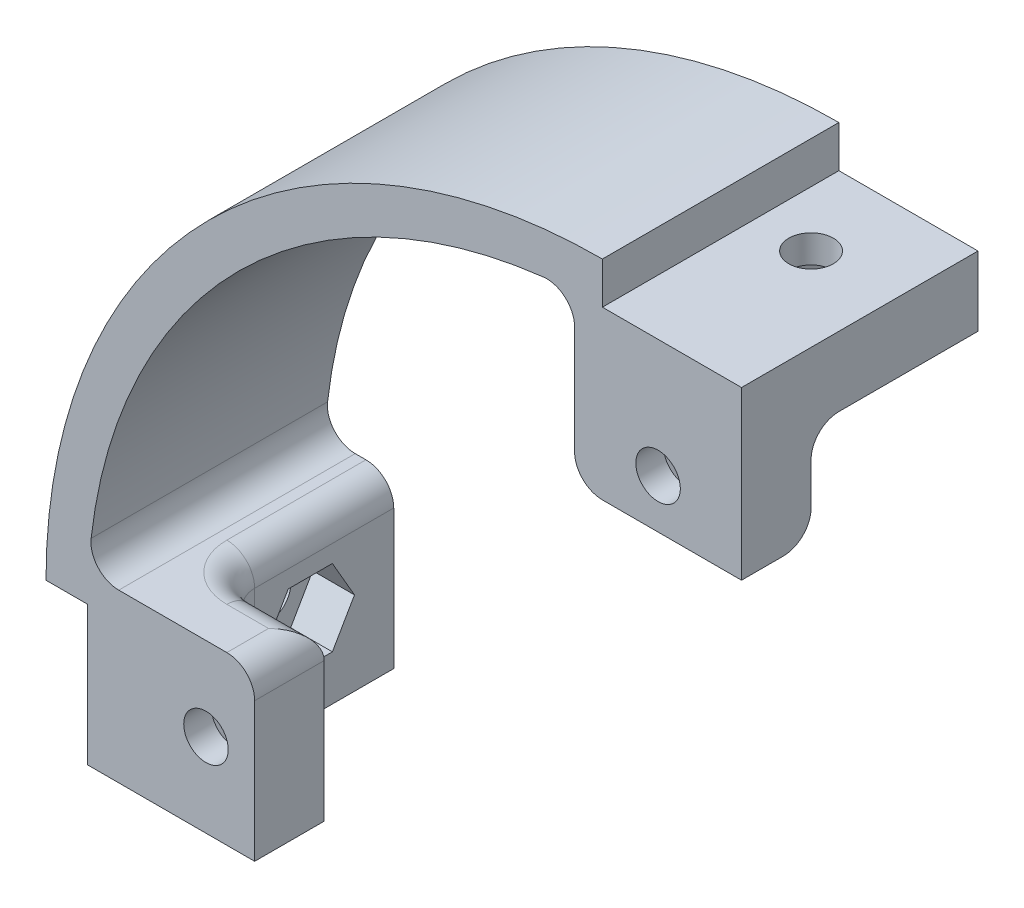
SolidWorks part; units mm, degrees
note: The reader was unsure of these and kept them because the rebuilt part matched: shared geometry of "Sketch4<3>", "Sketch6<3>", "Sketch8<3>", "Sketch9<3>".
ref_plane "Front Plane" through (0, 0, 0) normal (0, 0, 1) x (1, 0, 0)
ref_plane "Top Plane" through (0, 0, 0) normal (0, 1, 0) x (1, 0, 0)
ref_plane "Right Plane" through (0, 0, 0) normal (1, 0, 0) x (0, 0, -1)
sketch "Sketch1" plane through (0, 0, 0) normal (0, 0, 1) x (1, 0, 0)
  line L0 (0, 0) -> (3, 0)
  line L1 (40, 40) -> (40, 37)
  arc A0 (0, 0) -> (40, 40) centre (40, 0) cw
  arc A1 (3, 0) -> (40, 37) centre (40, 0) cw
  point P8 (40, 38.5)
  dimension "D1" = 40
  dimension "D2" = 3
extrude "Boss-Extrude1" add sketch "Sketch1" along normal blind 17
sketch "Sketch2" plane through (0, 0, 0) normal (0, -1, 0) x (1, 0, 0)
  line L0 (0, 0) -> (3, 0) construction
  line L1 (3, 17) -> (8, 17)
  line L2 (3, 17) -> (3, 0)
  line L3 (3, 0) -> (8, 0)
  line L4 (8, 17) -> (8, 0)
  line L5 (3, 17) -> (3, 0) construction
  line L6 (0, 17) -> (3, 17) construction
  dimension "D1" = 5
extrude "Boss-Extrude2" add sketch "Sketch2" along normal blind 10 and the other way blind 2
sketch "Sketch3" plane through (40, 0, 0) normal (1, 0, 0) x (0, 0, -1)
  line L0 (-17, 37) -> (-17, 40) construction
  line L1 (0, 37) -> (-17, 37)
  line L2 (0, 37) -> (0, 32)
  line L3 (0, 32) -> (-17, 32)
  line L4 (-17, 37) -> (-17, 32)
  dimension "D1" = 5
extrude "Boss-Extrude3" add sketch "Sketch3" along normal blind 10 and the other way blind 2
sketch "Sketch4" plane through (8, 0, 0) normal (1, 0, 0) x (0, 0, -1)
  line L1 (-17, 2) -> (-17, -10) construction
  line L2 (0, 2) -> (0, -10) construction
  line L4 (-4.4123, -6.75) -> (-2.8246, -4)
  line L5 (-2.8246, -4) -> (-4.4123, -1.25)
  line L6 (-4.4123, -1.25) -> (-7.5877, -1.25)
  line L7 (-7.5877, -1.25) -> (-9.1754, -4)
  line L8 (-9.1754, -4) -> (-7.5877, -6.75)
  line L9 (-7.5877, -6.75) -> (-4.4123, -6.75)
  circle A1 centre (-6, -4) radius 1.6
  circle A2 centre (-6, -4) radius 2.75 construction
  point P9 (-17, -4)
  dimension "D2" = 3.2
  dimension "D3" = 6
  dimension "D4" = 5.5
extrude "Cut-Extrude1" cut sketch "Sketch4" against normal blind 3
extrude "Cut-Extrude2" cut sketch "Sketch4<3>" against normal through all contours A1
sketch "Sketch4<3>" plane through (8, 0, 0) normal (1, 0, 0) x (0, 0, -1) same geometry as "Sketch4"
sketch "Sketch5" plane through (8, 0, 0) normal (1, 0, 0) x (0, 0, -1)
  line L0 (0, -10) -> (-17, -10) construction
  line L1 (-17, 2) -> (-12, 2)
  line L2 (-17, 2) -> (-17, -10)
  line L3 (-17, -10) -> (-12, -10)
  line L4 (-12, 2) -> (-12, -10)
  dimension "D1" = 5
extrude "Boss-Extrude4" add sketch "Sketch5" along normal blind 7
sketch "Sketch6" plane through (0, 0, 12) normal (0, 0, -1) x (-1, 0, 0)
  line L0 (-15, -10) -> (-8, -10) construction
  line L1 (-15, -10) -> (-15, 2) construction
  line L3 (-9.9123, -6.75) -> (-8.3246, -4)
  line L4 (-8.3246, -4) -> (-9.9123, -1.25)
  line L5 (-9.9123, -1.25) -> (-13.0877, -1.25)
  line L6 (-13.0877, -1.25) -> (-14.6754, -4)
  line L7 (-14.6754, -4) -> (-13.0877, -6.75)
  line L8 (-13.0877, -6.75) -> (-9.9123, -6.75)
  circle A1 centre (-11.5, -4) radius 1.6
  circle A2 centre (-11.5, -4) radius 2.75 construction
  point P5 (-11.5, -10)
  point P8 (-15, -4)
  dimension "D2" = 3.2
  dimension "D3" = 5.5
extrude "Cut-Extrude3" cut sketch "Sketch6" against normal blind 3
extrude "Cut-Extrude4" cut sketch "Sketch6<3>" against normal through all contours A1
sketch "Sketch6<3>" plane through (0, 0, 12) normal (0, 0, -1) x (-1, 0, 0) same geometry as "Sketch6"
sketch "Sketch7" plane through (0, 32, 0) normal (0, -1, 0) x (1, 0, 0)
  line L0 (38, 17) -> (38, 0) construction
  line L1 (50, 17) -> (38, 17)
  line L2 (50, 17) -> (50, 12)
  line L3 (50, 12) -> (38, 12)
  line L4 (38, 17) -> (38, 12)
  dimension "D1" = 5
extrude "Boss-Extrude5" add sketch "Sketch7" along normal blind 7
sketch "Sketch8" plane through (0, 32, 0) normal (0, -1, 0) x (1, 0, 0)
  line L0 (38, 0) -> (50, 0) construction
  line L2 (42.4123, 8.75) -> (40.8246, 6)
  line L3 (40.8246, 6) -> (42.4123, 3.25)
  line L4 (42.4123, 3.25) -> (45.5877, 3.25)
  line L5 (45.5877, 3.25) -> (47.1754, 6)
  line L6 (47.1754, 6) -> (45.5877, 8.75)
  line L7 (45.5877, 8.75) -> (42.4123, 8.75)
  circle A1 centre (44, 6) radius 1.6
  circle A2 centre (44, 6) radius 2.75 construction
  point P5 (44, 0)
  dimension "D2" = 3.2
  dimension "D3" = 6
  dimension "D4" = 5.5
extrude "Cut-Extrude5" cut sketch "Sketch8" against normal blind 3
extrude "Cut-Extrude6" cut sketch "Sketch8<3>" against normal through all contours A1
sketch "Sketch8<3>" plane through (0, 32, 0) normal (0, -1, 0) x (1, 0, 0) same geometry as "Sketch8"
sketch "Sketch9" plane through (0, 0, 12) normal (0, 0, -1) x (-1, 0, 0)
  line L0 (-38, 25) -> (-50, 25) construction
  line L1 (-50, 25) -> (-50, 32) construction
  line L3 (-45.5877, 25.75) -> (-42.4123, 25.75)
  line L4 (-42.4123, 25.75) -> (-40.8246, 28.5)
  line L5 (-40.8246, 28.5) -> (-42.4123, 31.25)
  line L6 (-42.4123, 31.25) -> (-45.5877, 31.25)
  line L7 (-45.5877, 31.25) -> (-47.1754, 28.5)
  line L8 (-47.1754, 28.5) -> (-45.5877, 25.75)
  circle A1 centre (-44, 28.5) radius 1.6
  circle A2 centre (-44, 28.5) radius 2.75 construction
  point P5 (-44, 25)
  point P8 (-50, 28.5)
  dimension "D1" = 5.5
  dimension "D2" = 3.2
extrude "Cut-Extrude7" cut sketch "Sketch9" against normal blind 3
extrude "Cut-Extrude8" cut sketch "Sketch9<3>" against normal through all contours A1
sketch "Sketch9<3>" plane through (0, 0, 12) normal (0, 0, -1) x (-1, 0, 0) same geometry as "Sketch9"
fillet "Fillet1" radius 2 11 edges at (3.0541, 2, 8.5) (11.5, 2, 12) (15, 2, 14.5) (8, -4, 12) (8, 2, 6) (38, 36.9459, 8.5) (38, 25, 14.5) (38, 32, 6) (38, 28.5, 12) (44, 25, 12) (44, 32, 12)
